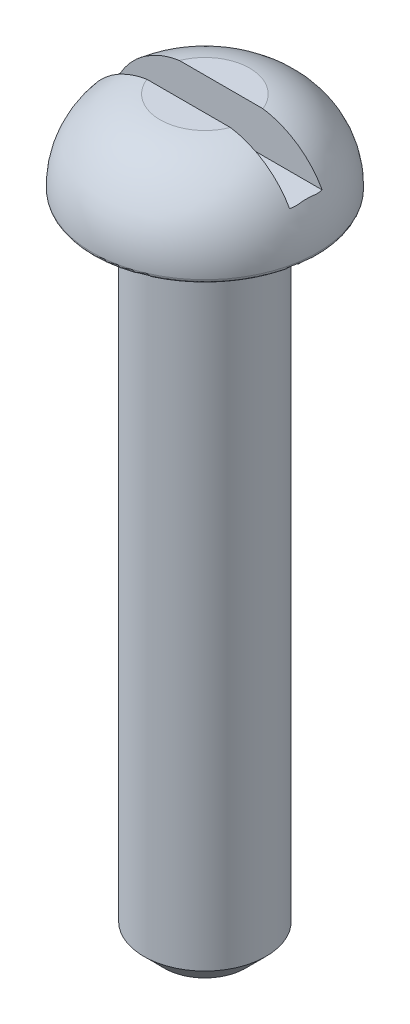
SolidWorks part; units mm, degrees
ref_plane "Спереди" through (0, 0, 0) normal (0, 0, 1) x (1, 0, 0)
ref_plane "Сверху" through (0, 0, 0) normal (0, 1, 0) x (1, 0, 0)
ref_plane "Справа" through (0, 0, 0) normal (1, 0, 0) x (0, 0, -1)
sketch "Эскиз1" plane through (0, 0, 0) normal (0, 0, 1) x (1, 0, 0)
  line L0 (2.75, 16) -> (1.5, 16)
  line L1 (0, 0) -> (0, 18.1)
  line L2 (1.5, 16) -> (1.5, 0.5)
  line L3 (1.5, 0.5) -> (1, 0)
  line L4 (1, 0) -> (0, 0)
  line L5 (0, 18.1) -> (1.1, 18.1)
  arc A0 (1.1, 18.1) -> (2.75, 16) centre (0.7797, 16.1501) cw
  dimension "D2" = 1.1
  dimension "D8" = 2.1
  dimension "D1" = 18.1
  dimension "D3" = 1.5
  dimension "D4" = 1
  dimension "D5" = 2.1
  dimension "D6" = 2.75
  dimension "D7" = 45
  dimension "D9" = 1.5
revolve "Повернуть1" add sketch "Эскиз1" angle 360 about L1
fillet "Скругление1" radius 0.1 1 edges at (0, 16, -2.75)
sketch "Эскиз3" plane through (0, 18.1, 0) normal (0, 1, 0) x (-1, 0, 0)
  line L1 (2.5, -0.4) -> (-2.5, -0.4)
  line L2 (2.5, -0.4) -> (2.5, 0.4)
  line L3 (2.5, 0.4) -> (-2.5, 0.4)
  line L4 (-2.5, -0.4) -> (-2.5, 0.4)
  dimension "D1" = 0.8
  dimension "D2" = 0.4
  dimension "D3" = 5
  dimension "D4" = 2.5
extrude "Вырез-Вытянуть2" cut sketch "Эскиз3" against normal blind 1
ref_axis "Ось1" through (0, -104.1565, 0) along (0, 1, 0)
